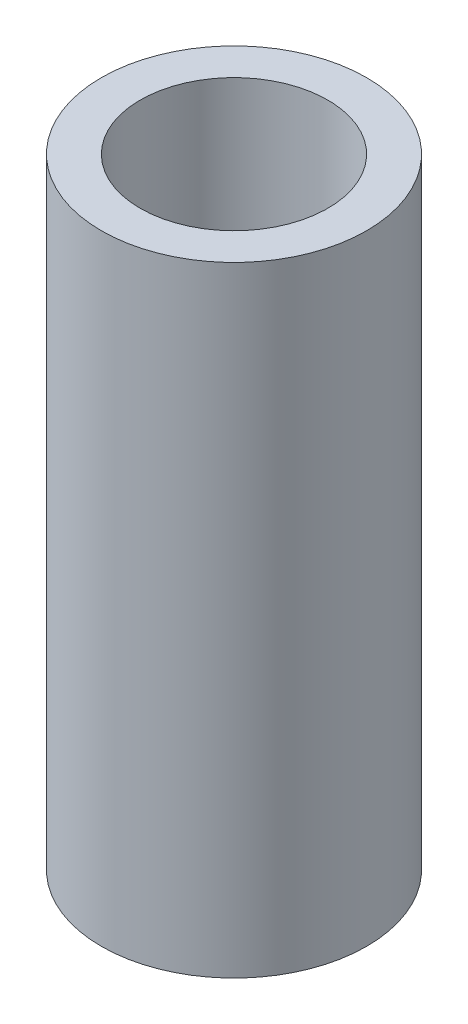
SolidWorks part; units mm, degrees
ref_plane "Front Plane" through (0, 0, 0) normal (0, 0, 1) x (1, 0, 0)
ref_plane "Top Plane" through (0, 0, 0) normal (0, 1, 0) x (1, 0, 0)
ref_plane "Right Plane" through (0, 0, 0) normal (1, 0, 0) x (0, 0, -1)
sketch "Sketch1" plane through (0, 0, 0) normal (0, 1, 0) x (1, 0, 0)
  circle A0 centre (0, 0) radius 10
  dimension "SLEEVE_OD" = 20
extrude "Boss-Extrude1" add sketch "Sketch1" along normal blind 46.7295
sketch "Sketch2" plane through (0, 0, 0) normal (0, 1, 0) x (1, 0, 0)
  circle A0 centre (0, 0) radius 7.073
  dimension "BORE_D" = 14.146
extrude "Cut-Extrude1" cut sketch "Sketch2" along normal through all
chamfer "Chamfer1" distance 1.496 angle 67.474 rebuild error yes
